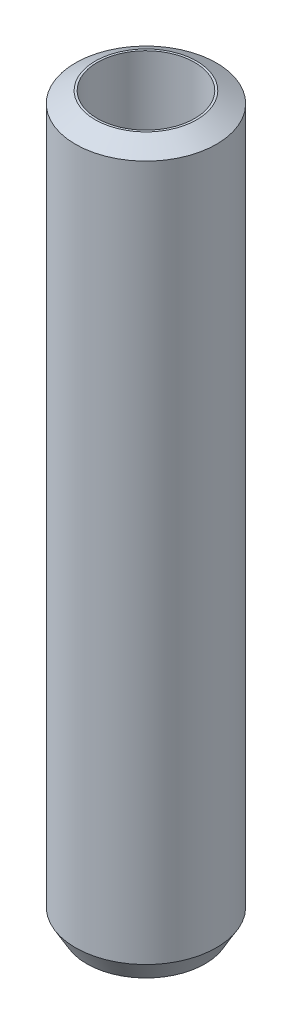
SolidWorks part; units mm, degrees
ref_plane "Front Plane" through (0, 0, 0) normal (0, 0, 1) x (1, 0, 0)
ref_plane "Top Plane" through (0, 0, 0) normal (0, 1, 0) x (1, 0, 0)
ref_plane "Right Plane" through (0, 0, 0) normal (1, 0, 0) x (0, 0, -1)
sketch "Sketch1" plane through (0, 0, 0) normal (0, 1, 0) x (1, 0, 0)
  circle A0 centre (0, 0) radius 35
  dimension "SHAFT_OD" = 70
extrude "Boss-Extrude1" add sketch "Sketch1" along normal blind 360.7244
sketch "Sketch2" plane through (0, 0, 0) normal (0, 1, 0) x (1, 0, 0)
  circle A0 centre (0, 0) radius 24.16
  dimension "BORE_D" = 48.32
extrude "Cut-Extrude1" cut sketch "Sketch2" along normal through all
chamfer "Chamfer1" distance 5.647 angle 60 2 edges at (0, 360.7244, 35) (0, 0, 35) first distance on face at (0, 360.7244, 35) first distance on face at (0, 0, 24.16)
